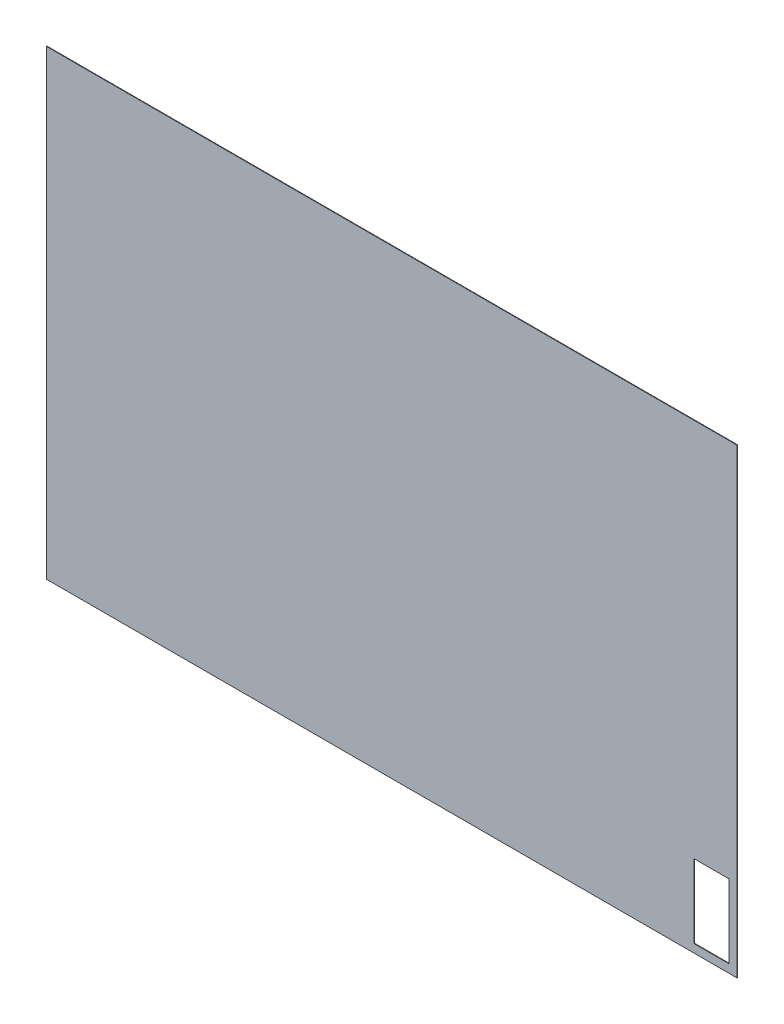
SolidWorks part; units mm, degrees
ref_plane "Front Plane" through (0, 0, 0) normal (0, 0, 1) x (1, 0, 0)
ref_plane "Top Plane" through (0, 0, 0) normal (0, 1, 0) x (1, 0, 0)
ref_plane "Right Plane" through (0, 0, 0) normal (1, 0, 0) x (0, 0, -1)
sketch "Sketch1" plane through (0, 0, 0) normal (0, 0, 1) x (1, 0, 0)
  line L1 (0, 0) -> (2500, 0)
  line L2 (0, 0) -> (0, 1670)
  line L3 (0, 1670) -> (2500, 1670)
  line L4 (2500, 0) -> (2500, 1670)
  line L5 (2470, 30) -> (2344, 30)
  line L6 (2470, 30) -> (2470, 296)
  line L7 (2470, 296) -> (2344, 296)
  line L8 (2344, 30) -> (2344, 296)
  dimension "D1" = 2500
  dimension "D2" = 1670
  dimension "D3" = 30
  dimension "D4" = 30
  dimension "D5" = 126
  dimension "D6" = 266
extrude "Boss-Extrude1" add sketch "Sketch1" along normal blind 2
